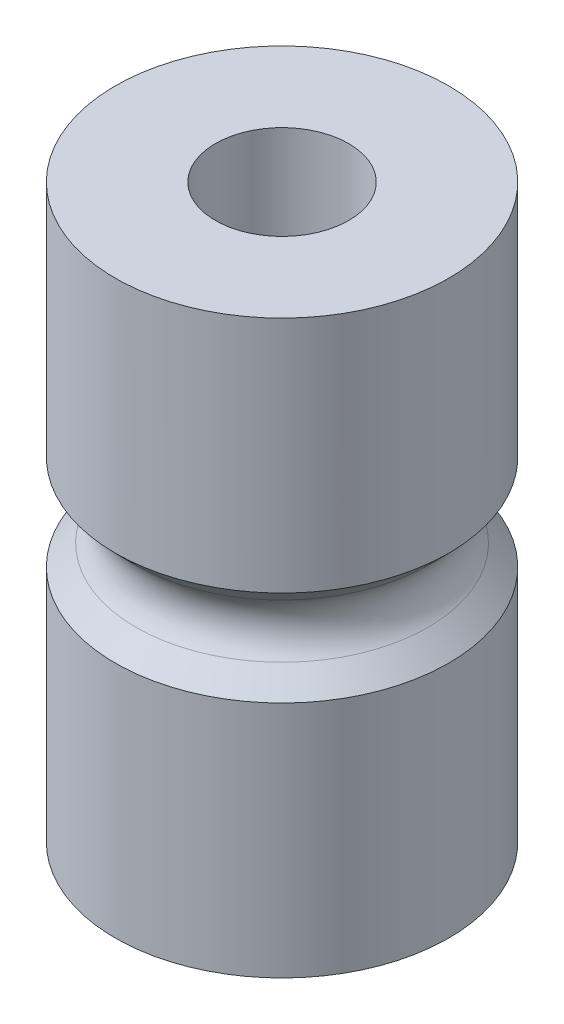
SolidWorks part; units mm, degrees
ref_plane "Front Plane" through (0, 0, 0) normal (0, 0, 1) x (1, 0, 0)
ref_plane "Top Plane" through (0, 0, 0) normal (0, 1, 0) x (1, 0, 0)
ref_plane "Right Plane" through (0, 0, 0) normal (1, 0, 0) x (0, 0, -1)
sketch "Sketch2" plane through (0, 0, 0) normal (0, 0, 1) x (1, 0, 0)
  line L0 (0, 0) -> (4.445, 0) construction
  line L1 (16.7951, 0) -> (16.7951, 19.05) construction
  line L2 (4.445, 0) -> (11.1125, 0)
  line L3 (4.445, 0) -> (4.445, 38.1)
  line L4 (4.445, 38.1) -> (11.1125, 38.1)
  line L5 (11.1125, 0) -> (11.1125, 15.875)
  line L6 (7.9375, 19.05) -> (11.1125, 15.875)
  line L7 (7.9375, 19.05) -> (11.1125, 22.225)
  line L8 (11.1125, 22.225) -> (11.1125, 38.1)
  line L9 (0, 0) -> (0, 30.073) construction
  dimension "D1" = 4.445
  dimension "D2" = 38.1
  dimension "D3" = 11.1125
  dimension "D4" = 19.05
  dimension "D5" = 3.175
  dimension "D6" = 45
  dimension "D7" = 6.35
revolve "Revolve1" add sketch "Sketch2" angle 360 about L9
fillet "Fillet1" radius 2.54 1 edges at (0, 19.05, -7.9375)
